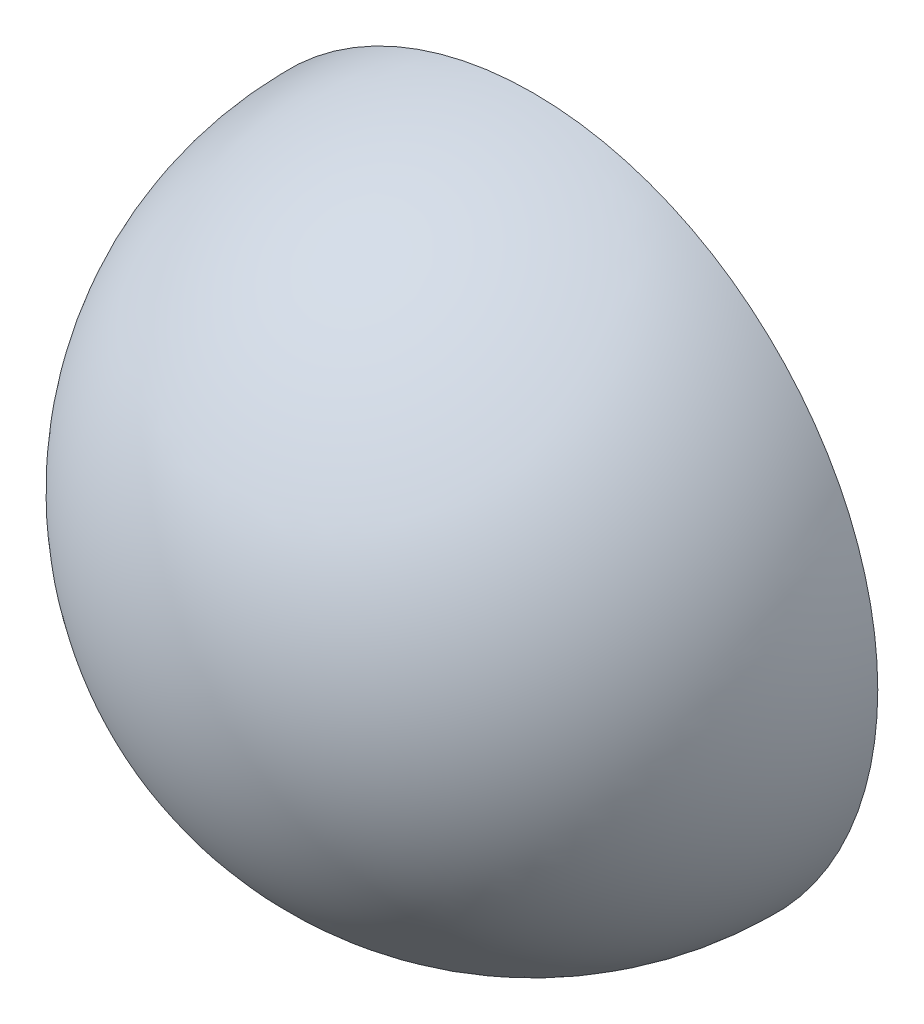
SolidWorks part; units mm, degrees
ref_plane "Front Plane" through (0, 0, 0) normal (0, 0, 1) x (1, 0, 0)
ref_plane "Top Plane" through (0, 0, 0) normal (0, 1, 0) x (1, 0, 0)
ref_plane "Right Plane" through (0, 0, 0) normal (1, 0, 0) x (0, 0, -1)
sketch "Sketch1" plane through (0, 0, 0) normal (1, 0, 0) x (0, 0, -1)
  line L0 (0, 40) -> (0, -40)
  line L1 (-89.3131, 0) -> (23.003, 0) construction
  arc A0 (0, 40) -> (0, -40) centre (0, 0) ccw
  dimension "D1" = 80
revolve "Revolve4" add sketch "Sketch1" angle 360 about L1 region at (0, 16.9765, 16.9765)
